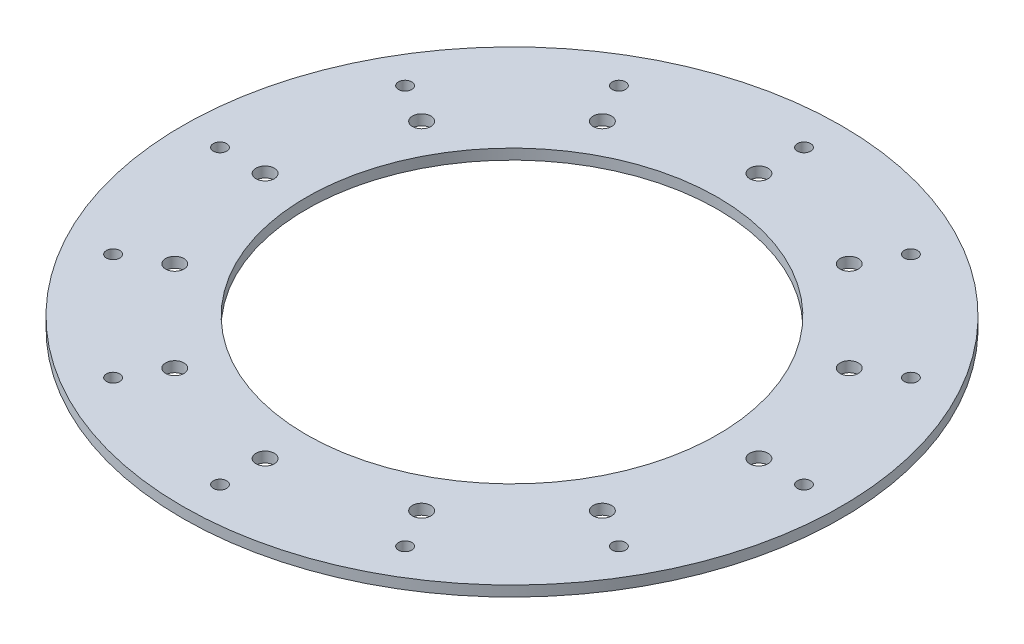
SolidWorks part; units mm, degrees
material "1060 Alloy"
ref_plane "Ebene vorne" through (0, 0, 0) normal (0, 0, 1) x (1, 0, 0)
ref_plane "Ebene oben" through (0, 0, 0) normal (0, 1, 0) x (1, 0, 0)
ref_plane "Ebene rechts" through (0, 0, 0) normal (1, 0, 0) x (0, 0, -1)
sketch "Sketch1" plane through (0, 0, 0) normal (0, 1, 0) x (1, 0, 0)
  circle A0 centre (0, 0) radius 49.3
  circle A1 centre (0, 0) radius 79
  dimension "D1" = 158
  dimension "D2" = 98.6
extrude "Boss-Extrude1" add sketch "Sketch1" along normal blind 2.5
sketch "Sketch2" plane through (0, 2.5, 0) normal (0, 1, 0) x (1, 0, 0)
  circle A0 centre (0, 70) radius 1.6
  circle A1 centre (35, 60.6218) radius 1.6
  circle A2 centre (60.6218, 35) radius 1.6
  circle A3 centre (70, 0) radius 1.6
  circle A4 centre (60.6218, -35) radius 1.6
  circle A5 centre (35, -60.6218) radius 1.6
  circle A6 centre (0, -70) radius 1.6
  circle A7 centre (-35, -60.6218) radius 1.6
  circle A8 centre (-60.6218, -35) radius 1.6
  circle A9 centre (-70, 0) radius 1.6
  circle A10 centre (-60.6218, 35) radius 1.6
  circle A11 centre (-35, 60.6218) radius 1.6
  point P28 (0, 0)
  dimension "D1" = 3.2
  dimension "D2" = 70
  dimension "D3" = 12
extrude "Cut-Extrude1" cut sketch "Sketch2" against normal through all
sketch "Sketch3" plane through (0, 2.5, 0) normal (0, 1, 0) x (1, 0, 0)
  circle A0 centre (0, 59.18) radius 2.2
  circle A1 centre (29.59, 51.2514) radius 2.2
  circle A2 centre (51.2514, 29.59) radius 2.2
  circle A3 centre (59.18, 0) radius 2.2
  circle A4 centre (51.2514, -29.59) radius 2.2
  circle A5 centre (29.59, -51.2514) radius 2.2
  circle A6 centre (0, -59.18) radius 2.2
  circle A7 centre (-29.59, -51.2514) radius 2.2
  circle A8 centre (-51.2514, -29.59) radius 2.2
  circle A9 centre (-59.18, 0) radius 2.2
  circle A10 centre (-51.2514, 29.59) radius 2.2
  circle A11 centre (-29.59, 51.2514) radius 2.2
  point P2 (0, 0)
  point P28 (0, 0)
  dimension "D1" = 4.4
  dimension "D3" = 118.36
  dimension "D2" = 12
extrude "Cut-Extrude2" cut sketch "Sketch3" against normal through all
